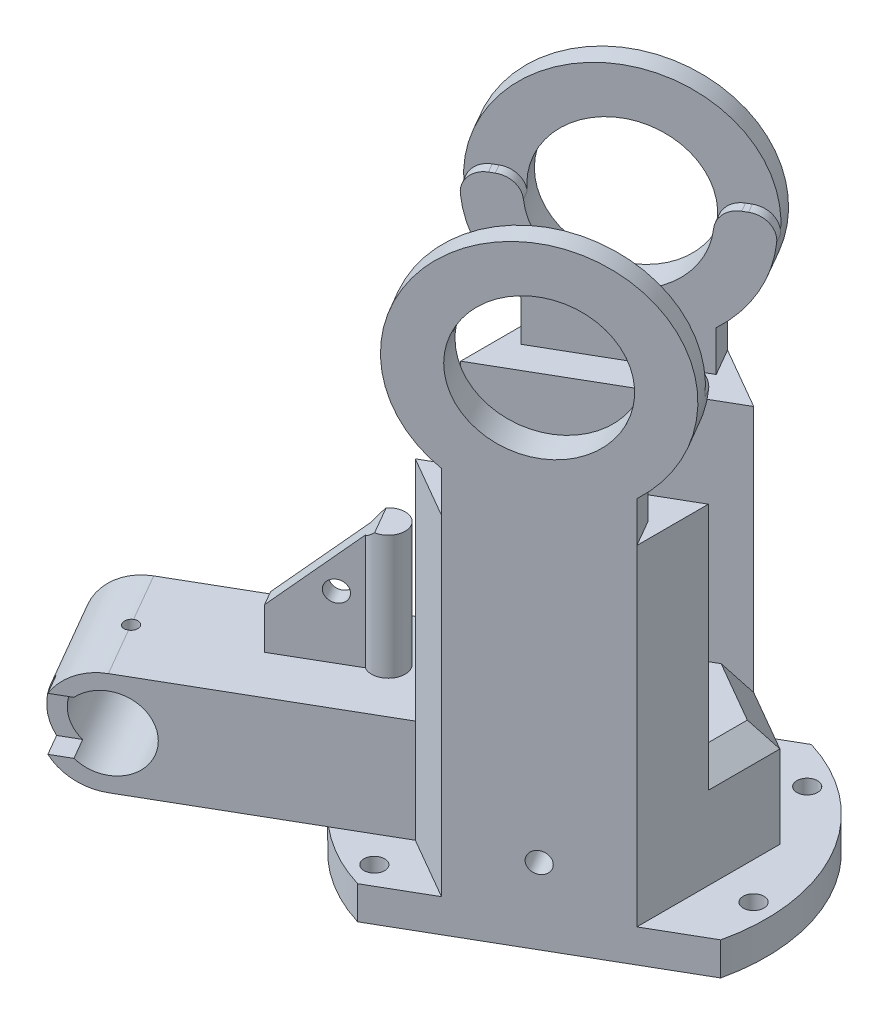
SolidWorks part; units mm, degrees
ref_plane "Front Plane" through (0, 0, 0) normal (0, 0, 1) x (1, 0, 0)
ref_plane "Top Plane" through (0, 0, 0) normal (0, 1, 0) x (1, 0, 0)
ref_plane "Right Plane" through (0, 0, 0) normal (1, 0, 0) x (0, 0, -1)
sketch "Sketch4" plane through (0, 0, 0) normal (0, 1, 0) x (1, 0, 0)
  circle A1 centre (0, 0) radius 55.88
  dimension "D2" = 111.76
extrude "Boss-Extrude2" add sketch "Sketch4" along normal blind 10.16
sketch "Sketch8" plane through (0, 10.16, 0) normal (0, 1, 0) x (1, 0, 0)
  line L1 (0, 43.9941) -> (-38.1, 21.997)
  line L2 (-38.1, 21.997) -> (-38.1, -21.997)
  line L3 (-38.1, -21.997) -> (0, -43.9941)
  line L4 (0, -43.9941) -> (38.1, -21.997)
  line L5 (38.1, -21.997) -> (38.1, 21.997)
  line L6 (38.1, 21.997) -> (0, 43.9941)
  circle A0 centre (0, 0) radius 38.1 construction
  dimension "D1" = 76.2
extrude "Boss-Extrude4" add sketch "Sketch8" along normal blind 101.6
sketch "Sketch9" plane through (-19.05, 0, -32.9956) normal (-0.5, 0, -0.866) x (-0.866, 0, 0.5)
  line L1 (21.997, 111.76) -> (-21.997, 111.76)
  line L2 (21.997, 111.76) -> (21.997, 124.226)
  line L4 (-21.997, 111.76) -> (-21.997, 124.226)
  arc A2 (21.997, 124.226) -> (-21.997, 124.226) centre (0, 152.4) ccw
extrude "Boss-Extrude5" add sketch "Sketch9" against normal blind 9.525
sketch "Sketch10" plane through (19.05, 0, 32.9956) normal (0.5, 0, 0.866) x (0.866, 0, -0.5)
  line L3 (-21.997, 111.76) -> (21.997, 111.76)
  line L4 (21.997, 111.76) -> (21.997, 124.226)
  line L5 (-21.997, 124.226) -> (-21.997, 111.76)
  line L6 (-21.997, 111.76) -> (21.997, 111.76)
  line L7 (21.997, 111.76) -> (21.997, 124.226)
  line L8 (-21.997, 124.226) -> (-21.997, 111.76)
  arc A1 (21.997, 124.226) -> (-21.997, 124.226) centre (0, 152.4) ccw
  arc A4 (21.997, 124.226) -> (-21.997, 124.226) centre (0, 152.4) ccw
  dimension "D1" = 0
extrude "Boss-Extrude6" add sketch "Sketch10" against normal blind 9.525
sketch "Sketch12" plane through (-19.05, 0, -32.9956) normal (-0.5, 0, -0.866) x (-0.866, 0, 0.5)
  circle A0 centre (0, 152.4) radius 21.5
  dimension "D1" = 43
extrude "Cut-Extrude4" cut sketch "Sketch12" against normal up to surface (76.2 mm away) up to face at (19.05, 92.7017, 32.9956)
sketch "Sketch13" plane through (-19.05, 0, 10.9985) normal (-0.866, 0, 0.5) x (0.5, 0, 0.866)
  line L0 (0, 111.76) -> (0, 10.16) construction
  line L1 (-19.05, 41.91) -> (19.05, 41.91)
  line L2 (-19.05, 41.91) -> (-19.05, 111.76)
  line L3 (-19.05, 111.76) -> (19.05, 111.76)
  line L4 (19.05, 41.91) -> (19.05, 111.76)
  line L5 (-19.05, 41.91) -> (19.05, 111.76) construction
  line L6 (-19.05, 111.76) -> (19.05, 41.91) construction
  line L7 (-38.1, 111.76) -> (0, 111.76) construction
  point P0 (0, 76.835)
  dimension "D1" = 69.85
  dimension "D2" = 0
  dimension "D3" = 38.1
extrude "Cut-Extrude5" cut sketch "Sketch13" against normal mid plane 152.4
sketch "Sketch14" plane through (-19.05, 0, -32.9956) normal (-0.5, 0, -0.866) x (-0.866, 0, 0.5)
  circle A0 centre (0, 124.7701) radius 3.8666
ref_plane "Plane1" through (0, 0, 0) normal (-0.5, 0, -0.866) x (-0.866, 0, 0.5)
sketch "Sketch17" plane through (0, 0, 0) normal (-0.5, 0, -0.866) x (-0.866, 0, 0.5)
  circle A0 centre (0, 152.4) radius 162.4584
  dimension "D1" = 324.9168
ref_plane "Plane3" through (38.1, 41.91, -21.997) normal (0, -1, 0) x (-1, 0, 0)
sketch "Sketch22" plane through (0, 0, 0) normal (-0.5, 0, -0.866) x (-0.866, 0, 0.5)
  line L5 (43.9941, 41.91) -> (102.101, 41.91)
  line L6 (102.101, 10.16) -> (43.9941, 10.16)
  line L8 (43.9941, 10.16) -> (21.997, 10.16)
  line L9 (21.997, 10.16) -> (21.997, 41.91)
  line L10 (21.997, 111.76) -> (21.997, 10.16) construction
  line L11 (21.997, 41.91) -> (43.9941, 41.91)
  arc A2 (102.101, 10.16) -> (102.101, 41.91) centre (102.101, 26.035) ccw
  circle A3 centre (0, 152.4) radius 162.4584 construction
  dimension "D1" = 31.75
ref_plane "Plane4" through (23.876, 0, 41.3544) normal (0.5, 0, 0.866) x (0.866, 0, -0.5)
extrude "Boss-Extrude10" add sketch "Sketch22" along normal mid plane 38.1
sketch "Sketch28" plane through (9.525, 0, 16.4978) normal (0.5, 0, 0.866) x (0.866, 0, -0.5)
  circle A0 centre (-102.101, 26.035) radius 11.2395
  dimension "D1" = 22.479
extrude "Cut-Extrude9" cut sketch "Sketch28" against normal up to surface (38.1 mm away) up to face at (-68.1724, 22.86, 17.3623)
sketch "Sketch29" plane through (9.525, 0, 16.4978) normal (0.5, 0, 0.866) x (0.866, 0, -0.5)
  line L1 (-104.4849, 17.907) -> (-122.1961, 17.907)
  line L2 (-104.4849, 17.907) -> (-104.4849, 34.163)
  line L3 (-104.4849, 34.163) -> (-122.1961, 34.163)
  line L4 (-122.1961, 17.907) -> (-122.1961, 34.163)
  line L5 (-104.4849, 17.907) -> (-122.1961, 34.163) construction
  line L6 (-104.4849, 34.163) -> (-122.1961, 17.907) construction
  circle A0 centre (-102.101, 26.035) radius 11.2395 construction
  arc A1 (-102.101, 41.91) -> (-102.101, 10.16) centre (-102.101, 26.035) ccw construction
  circle A2 centre (-102.101, 26.035) radius 11.2395
  circle A3 centre (-102.101, 26.035) radius 11.2395
  arc A4 (-102.101, 41.91) -> (-102.101, 10.16) centre (-102.101, 26.035) ccw
  point P0 (-113.3405, 26.035)
  circle M3 centre (-102.101, 26.035) radius 11.2395
  arc M7 (-102.101, 41.91) -> (-102.101, 10.16) centre (-102.101, 26.035) ccw
  dimension "D1" = 16.256
  dimension "D2" = 0
extrude "Cut-Extrude10" cut sketch "Sketch29" against normal blind 7.366 contours L3 L1 M3 M7 region at (-89.8086, 26.035, 73.8481)
chamfer "Chamfer1" distance 6.35 angle 45 2 edges at (38.1, 41.91, -10.9985) (28.575, 41.91, -27.4963)
sketch "Sketch30" plane through (0, 41.91, 0) normal (0, 1, 0) x (1, 0, 0)
  line L0 (-97.9471, -34.5527) -> (-78.8971, -67.5483) construction
  circle A0 centre (-88.4221, -51.0505) radius 2.1
  dimension "D1" = 4.2
extrude "Cut-Extrude11" cut sketch "Sketch30" against normal blind 7.366
sketch "Sketch31" plane through (0, 10.16, 0) normal (0, 1, 0) x (1, 0, 0)
  circle A0 centre (0, 0) radius 49.53 construction
  circle A4 centre (-49.089, 6.5948) radius 3.175
  circle A5 centre (26.9253, 41.5722) radius 3.175
  dimension "D1" = 6.35
  dimension "D2" = 99.06
  dimension "D3" = 6.35
extrude "Cut-Extrude12" cut sketch "Sketch31" against normal through all
mirror "Mirror1" about plane through (0, 0, 0) normal (-0.5, 0, -0.866) of "Cut-Extrude12"
sketch "Sketch33" plane through (0, 41.91, 0) normal (0, 1, 0) x (1, 0, 0)
  line L0 (140.6931, 81.2292) -> (-140.6931, -81.2292) construction
  line L5 (-43.4119, -22.0798) -> (-63.0924, -33.4424)
  line L6 (-63.0924, -33.4424) -> (-61.8003, -35.6804)
  line L7 (-61.8003, -35.6804) -> (-60.5427, -37.8586)
  line L8 (-60.5427, -37.8586) -> (-40.9154, -26.5041)
  arc A0 (-40.9154, -26.5041) -> (-43.4119, -22.0798) centre (-38.2434, -22.0798) ccw
extrude "Boss-Extrude11" add sketch "Sketch33" along normal blind 38.1
chamfer "Chamfer2" distance 25.4 angle 45 1 edges at (-61.8176, 80.01, 35.6505)
sketch "Sketch34" plane through (-1.2921, 0, -2.238) normal (-0.5, 0, -0.866) x (-0.866, 0, 0.5)
  circle A0 centre (55.1848, 61.1591) radius 3.175
  dimension "D1" = 6.35
extrude "Cut-Extrude13" cut sketch "Sketch34" against normal up to surface (5.0994 mm away) up to face at (-50.7291, 53.9288, 32.1813)
sketch "Sketch35" plane through (19.05, 0, 32.9956) normal (0.5, 0, 0.866) x (0.866, 0, -0.5)
  circle A0 centre (0, 23.2801) radius 3.175
  dimension "D1" = 6.35
extrude "Cut-Extrude14" cut sketch "Sketch35" against normal through all
sketch "Sketch36" plane through (-19.05, 0, 10.9985) normal (-0.866, 0, 0.5) x (0.5, 0, 0.866)
  line L0 (0, 0) -> (0, 199.814) construction
  line L1 (-31.75, 193.0158) -> (31.75, 193.0158)
  line L2 (-31.75, 193.0158) -> (-31.75, 156.3059)
  line L3 (-31.75, 156.3059) -> (31.75, 156.3059)
  line L4 (31.75, 193.0158) -> (31.75, 156.3059)
  line L5 (-55.88, 0) -> (55.88, 0) construction
  line L6 (0, 17.4625) -> (0, -17.4625) construction
  point P10 (0, 156.3059)
  dimension "D1" = 63.5
extrude "Cut-Extrude15" cut sketch "Sketch36" against normal mid plane 127
fillet "Fillet1" radius 6.35 6 edges at (-33.391, 156.3059, -15.5504) (3.2285, 156.3059, -36.6926) (15.6887, 156.3059, -43.8865) (45.8512, 156.3059, 8.3564) (-15.6887, 156.3059, 43.8865) (-45.8512, 156.3059, -8.3564)
sketch "Sketch37" plane through (0, 10.16, 0) normal (0, 1, 0) x (1, 0, 0)
  line L0 (-50.0053, 15.1235) -> (11.9053, 50.8676)
  line L1 (11.9053, 50.8676) -> (28.9191, 60.6905)
  line L2 (28.9191, 60.6905) -> (-19.05, 57.412)
  line L3 (-19.05, 57.412) -> (-73.371, 21.5973)
  line L4 (-73.371, 21.5973) -> (-72.242, 5.0781)
  line L5 (-38.7925, 21.5973) -> (-72.242, 2.2851)
  line L6 (-72.242, 2.2851) -> (-72.242, 5.0781)
  line L7 (19.05, -32.9956) -> (-27.0073, -59.5867)
  line L8 (-11.9053, -50.8676) -> (50.0053, -15.1235) construction
  line L9 (-27.0073, -59.5867) -> (28.9191, -77.7073)
  line L10 (28.9191, -77.7073) -> (77.1234, -25.4322)
  line L11 (77.1234, -25.4322) -> (71.516, -6.0778)
  line L12 (19.05, -32.9956) -> (63.6735, -7.2322)
  line L13 (63.6735, -7.2322) -> (71.516, -6.0778)
  line M7 (-38.1, 21.997) -> (0, 43.9941)
  line M10 (38.1, -21.997) -> (0, -43.9941)
  arc M13 (-35.9695, -42.7641) -> (-55.0195, -9.7685) centre (0, 0) ccw
extrude "Cut-Extrude16" cut sketch "Sketch37" against normal through all contours L6 L5 L1 L2 L3 L4 M13 | L5 L0 L1 M7 M13 | L12 L7 M10 M13 | L13 L12 L7 L9 L10 L11 M13 region at (-22.6594, 10.16, -39.2473) region at (36.0455, 10.16, 46.8659) region at (22.6594, 10.16, 39.2473) region at (-63.9354, 10.16, -8.4411)
